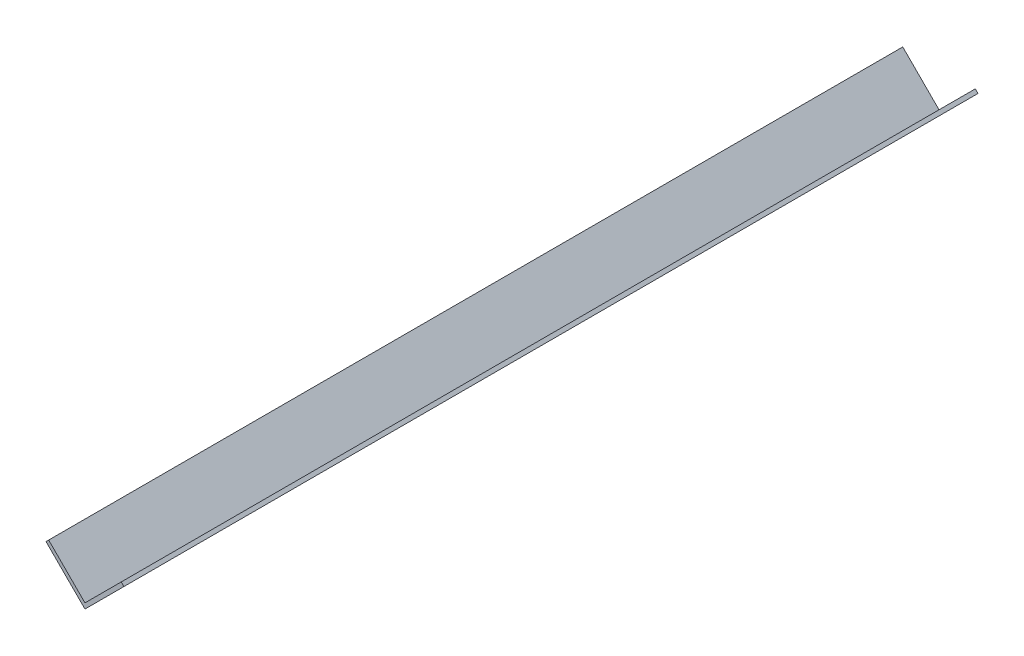
SolidWorks part; units mm, degrees
material "6061 Alloy"
ref_plane "Front Plane" through (0, 0, 0) normal (0, 0, 1) x (1, 0, 0)
ref_plane "Top Plane" through (0, 0, 0) normal (0, 1, 0) x (1, 0, 0)
ref_plane "Right Plane" through (0, 0, 0) normal (1, 0, 0) x (0, 0, -1)
sketch "Sketch1" plane through (0, 0, 0) normal (0, 0, 1) x (1, 0, 0)
  line L0 (0, 0) -> (-17.9605, 17.9605)
  line L1 (-17.9605, 17.9605) -> (-16.7257, 19.1953)
  line L2 (-16.7257, 19.1953) -> (0, 2.4696)
  line L3 (0, 2.4696) -> (16.7257, 19.1953)
  line L4 (16.7257, 19.1953) -> (17.9605, 17.9605)
  line L5 (17.9605, 17.9605) -> (0, 0)
  dimension "D1" = 1.7463
  dimension "D2" = 25.4
extrude "Boss-Extrude1" add sketch "Sketch1" along normal blind 393.7
